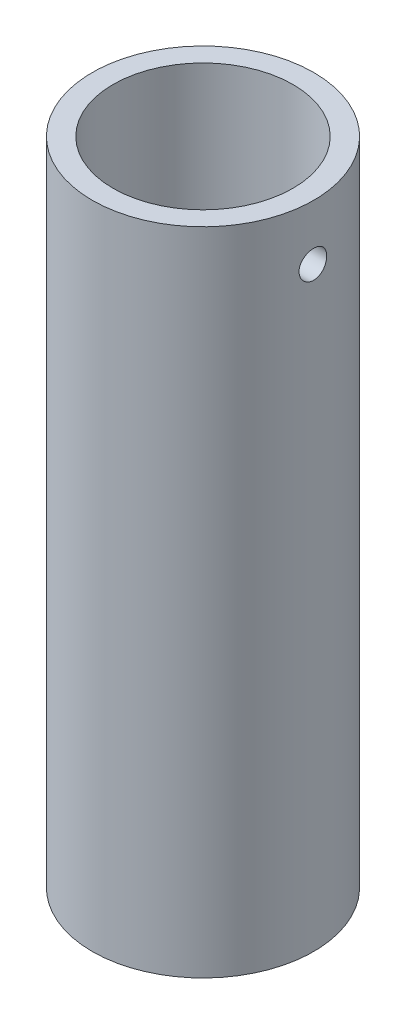
SolidWorks part; units mm, degrees
material "AISI 304"
ref_plane "Front Plane" through (0, 0, 0) normal (0, 0, 1) x (1, 0, 0)
ref_plane "Top Plane" through (0, 0, 0) normal (0, 1, 0) x (1, 0, 0)
ref_plane "Right Plane" through (0, 0, 0) normal (1, 0, 0) x (0, 0, -1)
sketch "Sketch3" plane through (0, 0, 0) normal (0, 1, 0) x (1, 0, 0)
  circle A0 centre (0, 0) radius 8
  dimension "D1" = 16
extrude "Extrude-Thin1" add sketch "Sketch3" along normal mid plane 47 thin contours A0 thin type one direction reverse wall 1.5
hole_wizard "Ø2.0mm Dowel Hole1" positions "3DSketch1" profile "Sketch4" hole size "Ø2.0" standard "ISO" end condition up to next
sketch3d "3DSketch1"
  point P0 (8, 19.5, 0)
  point P4 (6.5386, 9.7608, -4.6094)
  point P5 (6.5382, 18.6017, 4.6099)
  point P6 (0, 0, 0)
  dimension "D1" = 43
sketch "Sketch4" plane through (8, 19.5, 0) normal (0, 1, 0) x (0, 0, -1)
  line L0 (0, 0) -> (0, 1.5)
  line L1 (0, 1.5) -> (1, 1.5)
  line L2 (1, 1.5) -> (1, 0)
  line L5 (1, 0) -> (0, 0)
  line L11 (0, -6.35) -> (0, 107.95) construction
  dimension "Thru Hole Dia." = 2
  dimension "Thru Hole Depth" = 1.5
